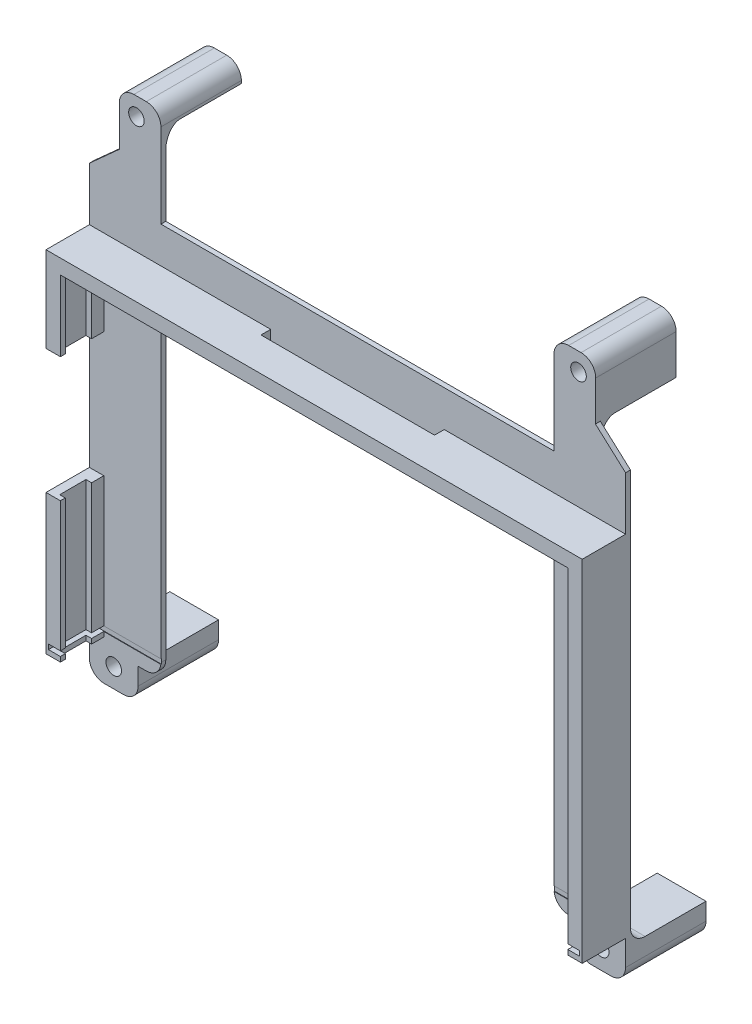
SolidWorks part; units mm, degrees
ref_plane "Front Plane" through (0, 0, 0) normal (1, 0, 0) x (0, 1, 0)
ref_plane "Top Plane" through (0, 0, 0) normal (0, 0, 1) x (0, 1, 0)
ref_plane "Right Plane" through (0, 0, 0) normal (0, 1, 0) x (-1, 0, 0)
sketch "Sketch1" plane through (0, 0, 0) normal (0, 0, 1) x (0, 1, 0)
  line L0 (-47.4715, -54.7542) -> (-54.0067, -54.7542)
  line L1 (-54.0067, -44.7542) -> (-54.0067, -54.7542)
  line L6 (-47.4715, -44.7542) -> (-54.0067, -44.7542)
  line L7 (-47.4715, -44.7542) -> (-47.4715, -54.7542)
  line L8 (42.478, -48.5761) -> (50.1367, -40.0774)
  line L9 (50.1367, -40.0774) -> (53.6912, -40.0774)
  line L10 (53.6912, -40.0774) -> (53.6912, -48.6408)
  line L11 (53.6912, -48.6408) -> (42.478, -48.5761)
  line L12 (53.6912, 49.1325) -> (42.478, 49.0678)
  line L13 (53.6912, 40.569) -> (53.6912, 49.1325)
  line L14 (50.1367, 40.569) -> (53.6912, 40.569)
  line L15 (42.478, 49.0678) -> (50.1367, 40.569)
  line L16 (-47.4715, 45.2458) -> (-47.4715, 55.2458)
  line L17 (-47.4715, 45.2458) -> (-54.0067, 45.2458)
  line L18 (-54.0067, 45.2458) -> (-54.0067, 55.2458)
  line L19 (-47.4715, 55.2458) -> (-54.0067, 55.2458)
  circle A0 centre (-50.0067, -49.7542) radius 1.6
  circle A1 centre (49.9933, -45.1018) radius 1.6
  circle A2 centre (49.9933, 45.5934) radius 1.6
  circle A3 centre (-50.0067, 50.2458) radius 1.6
extrude "Boss-Extrude1" add sketch "Sketch1" along normal blind 15.5
sketch "Sketch2" plane through (0, 0, 15.5) normal (0, 0, 1) x (1, 0, 0)
  line L0 (54.7542, -47.4715) -> (54.7542, -54.0067)
  line L1 (41.7542, -19.0067) -> (-42.2458, -19.0067) construction
  line L2 (-0.2458, -19.0067) -> (-0.2458, 62.4675) construction
  line L3 (-49.1325, 53.6912) -> (-49.0678, 42.478)
  line L4 (-40.569, 53.6912) -> (-49.1325, 53.6912)
  line L5 (44.7542, -54.0067) -> (54.7542, -54.0067)
  line L6 (44.7542, -47.4715) -> (44.7542, -54.0067)
  line L7 (40.0774, 53.6912) -> (40.0774, 33.4233)
  line L9 (-40.569, 53.6912) -> (-40.569, 33.4233)
  line L10 (-45.2458, -47.4715) -> (-40.569, -47.4715)
  line L11 (40.0774, 53.6912) -> (48.6408, 53.6912)
  line L12 (48.6408, 53.6912) -> (48.5761, 42.478)
  line L13 (-53.4458, -43.9132) -> (-53.4458, -44.8132)
  line L14 (-55.2458, -44.8132) -> (54.7542, -44.8132) construction
  line L15 (-45.2458, -47.4715) -> (-45.2458, -54.0067)
  line L16 (-45.2458, -54.0067) -> (-55.2458, -54.0067)
  line L17 (-55.2458, -47.4715) -> (-55.2458, -54.0067)
  line L18 (44.7542, -47.4715) -> (40.0774, -47.4715)
  line L19 (40.0774, -47.4715) -> (40.0774, 20.9868)
  line L20 (48.5761, 42.478) -> (54.7542, 36.9106)
  line L21 (54.7542, -47.4715) -> (54.7542, 36.9106)
  line L22 (40.0774, 20.9868) -> (-40.569, 20.9868)
  line L23 (40.0774, 33.4233) -> (-40.569, 33.4233)
  line L24 (-55.2458, -47.4715) -> (-55.2458, 36.9106)
  line L25 (-49.0678, 42.478) -> (-55.2458, 36.9106)
  line L26 (-40.569, -47.4715) -> (-40.569, 20.9868)
  line L27 (-52.317, -43.9132) -> (-52.317, -44.8132)
  line L28 (-49.1325, 53.6912) -> (-49.0678, 42.478)
  line L29 (-40.569, 53.6912) -> (-49.1325, 53.6912)
  line L31 (-53.4458, -43.9132) -> (52.9542, -43.9132) construction
  line L32 (52.9542, -43.9132) -> (52.9542, -44.8132)
  line L33 (-45.2458, -47.4715) -> (-45.2458, -54.0067)
  line L34 (-45.2458, -54.0067) -> (-55.2458, -54.0067)
  line L35 (-55.2458, -47.4715) -> (-55.2458, -54.0067)
  circle A0 centre (49.7542, -50.0067) radius 1.6
  circle A1 centre (45.1018, 49.9933) radius 1.6
  circle A2 centre (-45.5934, 49.9933) radius 1.6
  circle A3 centre (-50.2458, -50.0067) radius 1.6
  circle A4 centre (-45.5934, 49.9933) radius 1.6
  circle A5 centre (-50.2458, -50.0067) radius 1.6
  point P37 (-0.2458, 33.4233)
  point P38 (-0.2458, 20.9868)
  line M3 (48.5761, 42.478) -> (48.6408, 53.6912)
  line M4 (48.6408, 53.6912) -> (40.0774, 53.6912)
  line M5 (40.0774, 53.6912) -> (40.0774, 50.1367)
  line M6 (40.0774, 50.1367) -> (48.5761, 42.478)
  circle M7 centre (45.1018, 49.9933) radius 1.6
  dimension "D1" = 3.2
  dimension "D2" = 3.2
extrude "Boss-Extrude2" add sketch "Sketch2" along normal blind 1 contours L15 L26 L22 L19 L18 L6 L5 L0 L21 L20 L7 L23 L9 L4 L3 L25 L24 L17 L16 A2 A0 A3 M6 | M6 M3 M4 M5 M7 region at (53.2147, -50.7391, 15.5) region at (44.4212, 46.4122, 15.5)
sketch "Sketch3" plane through (0, 0, 16.5) normal (0, 0, 1) x (1, 0, 0)
  line L1 (-52.2958, 22.9868) -> (51.8042, 22.9868)
  line L2 (-52.2958, 22.9868) -> (-52.2958, 8.4399)
  line L3 (-52.2958, -42.8132) -> (-50.6497, -42.8132)
  line L4 (51.8042, 22.9868) -> (51.8042, -42.8132)
  line L5 (-52.2958, 22.9868) -> (51.8042, -42.8132) construction
  line L6 (-52.2958, -42.8132) -> (51.8042, 22.9868) construction
  line L20 (54.7542, 36.9106) -> (54.7542, -54.0067) construction
  line L21 (-55.2458, 25.9868) -> (54.7542, 25.9868)
  line L23 (40.0774, 20.9868) -> (-40.569, 20.9868) construction
  line L24 (-55.2458, 25.9868) -> (-55.2458, 8.4399)
  line L29 (-55.2458, -45.8132) -> (-52.2958, -45.8132)
  line L30 (54.7542, 25.9868) -> (54.7542, -45.8132)
  line L31 (-55.2458, 25.9868) -> (54.7542, -45.8132) construction
  line L32 (-55.2458, -45.8132) -> (54.7542, 25.9868) construction
  line L33 (-52.2958, -42.8132) -> (-52.2958, -45.8132)
  line L34 (51.8042, -42.8132) -> (51.8042, -45.8132)
  line L35 (51.8042, -45.8132) -> (54.7542, -45.8132)
  line L36 (50.1581, -42.8132) -> (51.8042, -42.8132)
  line L37 (-55.2458, 8.4399) -> (-52.2958, 8.4399)
  line L38 (-55.2458, -17.1408) -> (-52.2958, -17.1408)
  line L39 (-52.2958, -17.1408) -> (-52.2958, -42.8132)
  line L40 (-55.2458, -17.1408) -> (-55.2458, -45.8132)
  point P0 (-0.2458, -9.9132)
  point P5 (-0.2458, -9.9132)
  point P12 (-0.2458, -9.9132)
  point P20 (-0.2458, 20.9868)
  point P21 (-0.2458, -9.9132)
  line M14 (54.7542, -54.0067) -> (54.7542, 36.9106)
  line M24 (-55.2458, 36.9106) -> (-55.2458, -54.0067)
  dimension "D1" = 104.1
  dimension "D2" = 65.8
  dimension "D3" = 2
  dimension "D4" = 3
extrude "Boss-Extrude3" add sketch "Sketch3" along normal blind 2.5 contours L34 L35 L21 L29 L33 L2 L1 L4 M14 M24 | L33 L29 L40 L38 L39 region at (-53.6094, 15.7133, 16.5)
sketch "Sketch4" plane through (0, 0, 19) normal (0, 0, 1) x (1, 0, 0)
  line L0 (-0.2458, 22.9868) -> (-0.2458, -59.386) construction
  line L1 (-52.2958, 22.9868) -> (51.8042, 22.9868) construction
  line L2 (-55.2458, -45.8132) -> (54.7542, -45.8132) construction
  line L3 (-55.2458, 25.9868) -> (54.7542, 25.9868)
  line L4 (-55.2458, 25.9868) -> (-55.2458, 8.4399)
  line L5 (-55.2458, -45.8132) -> (-53.4458, -45.8132)
  line L6 (54.7542, 25.9868) -> (54.7542, -45.8132)
  line L7 (-55.2458, 25.9868) -> (54.7542, -45.8132) construction
  line L8 (-55.2458, -45.8132) -> (54.7542, 25.9868) construction
  line L9 (-53.4458, 24.0868) -> (52.9542, 24.0868)
  line L10 (-53.4458, 24.0868) -> (-53.4458, 8.4399)
  line L12 (52.9542, 24.0868) -> (52.9542, -43.9132)
  line L13 (-53.4458, 24.0868) -> (52.9542, -43.9132) construction
  line L14 (-53.4458, -43.9132) -> (52.9542, 24.0868) construction
  line L15 (-53.4458, -43.9132) -> (-53.4458, -45.8132)
  line L16 (52.9542, -43.9132) -> (52.9542, -45.8132)
  line L17 (52.9542, -45.8132) -> (54.7542, -45.8132)
  line L18 (-55.2458, 8.4399) -> (-53.4458, 8.4399)
  line L19 (-55.2458, 8.4399) -> (-52.2958, 8.4399) construction
  line L20 (-55.2458, -17.1408) -> (-53.4458, -17.1408)
  line L21 (-55.2458, -17.1408) -> (-52.2958, -17.1408) construction
  line L22 (-55.2458, -17.1408) -> (-55.2458, -45.8132)
  line L23 (-53.4458, -17.1408) -> (-53.4458, -43.9132)
  line L24 (-55.2458, -43.8132) -> (54.7542, -43.8132) construction
  point P4 (-0.2458, -9.9132)
  point P13 (-0.2458, -9.9132)
  dimension "D1" = 106.4
  dimension "D2" = 68
  dimension "D3" = 67.9
extrude "Boss-Extrude4" add sketch "Sketch4" along normal blind 5.4
sketch "Sketch5" plane through (0, 0, 24.4) normal (0, 0, 1) x (1, 0, 0)
  line L0 (-55.2458, 8.4399) -> (-52.2958, 8.4399)
  line L1 (-52.2958, 22.9868) -> (51.8042, 22.9868)
  line L2 (-52.2958, 22.9868) -> (-52.2958, 8.4399)
  line L4 (51.8042, 22.9868) -> (51.8042, -45.8132)
  line L5 (-55.2458, 25.9868) -> (54.7542, 25.9868)
  line L6 (-55.2458, 25.9868) -> (-55.2458, 8.4399)
  line L7 (-55.2458, -45.8132) -> (-52.2958, -45.8132)
  line L8 (54.7542, 25.9868) -> (54.7542, -45.8132)
  line L9 (-55.2458, -17.1408) -> (-52.2958, -17.1408)
  line L10 (51.8042, -45.8132) -> (54.7542, -45.8132)
  line L11 (-52.2958, -17.1408) -> (-52.2958, -45.8132)
  line L12 (-55.2458, -17.1408) -> (-55.2458, -45.8132)
extrude "Boss-Extrude5" add sketch "Sketch5" along normal blind 1
sketch "Sketch7" plane through (0, 0, 25.4) normal (0, 0, 1) x (1, 0, 0)
  line L0 (-54.7458, -43.8132) -> (54.2542, -43.8132)
  line L1 (54.2542, -43.8132) -> (54.2542, -44.8132)
  line L2 (54.2542, -44.8132) -> (-54.7458, -44.8132)
  line L3 (-54.7458, -44.8132) -> (-54.7458, -43.8132)
  line L4 (51.8042, -45.8132) -> (54.7542, -45.8132) construction
  line L5 (54.7542, -45.8132) -> (54.7542, 25.9868) construction
  line L6 (-55.2458, -17.1408) -> (-55.2458, -45.8132) construction
  dimension "D1" = 1
  dimension "D2" = 1
  dimension "D3" = 0.5
  dimension "D4" = 0.5
extrude "Cut-Extrude1" cut sketch "Sketch7" against normal blind 9
fillet "Fillet1" radius 3 10 edges at (48.6408, 53.6912, 8.25) (-49.1325, 53.6912, 8.25) (-40.569, -47.4715, 16) (-55.2458, -54.0067, 8.25) (-45.2458, -54.0067, 8.25) (40.0774, -47.4715, 16) (44.7542, -54.0067, 8.25) (54.7542, -54.0067, 8.25) (40.0774, 53.6912, 8.25) (-40.569, 53.6912, 8.25)
fillet "Fillet2" radius 3 4 edges at (-50.2458, -47.4715, 15.5) (-44.8184, 46.3073, 15.5) (44.3268, 46.3073, 15.5) (49.7542, -47.4715, 15.5)
sketch "Sketch8" plane through (0, 25.9868, 0) normal (0, 1, 0) x (-1, 0, 0)
  line L0 (-40.0774, 16.5) -> (40.569, 16.5) construction
  line L1 (-17.5542, 16.5) -> (18.0458, 16.5)
  line L2 (-17.5542, 16.5) -> (-17.5542, 18.5)
  line L3 (-17.5542, 18.5) -> (18.0458, 18.5)
  line L4 (18.0458, 16.5) -> (18.0458, 18.5)
  line L5 (0.2458, 25.4) -> (0.2458, 15.5) construction
  line L6 (-54.7542, 25.4) -> (55.2458, 25.4) construction
  line L7 (-40.0774, 15.5) -> (40.569, 15.5) construction
  dimension "D1" = 2
  dimension "D2" = 17.8
  dimension "D3" = 17.8
extrude "Cut-Extrude2" cut sketch "Sketch8" against normal blind 2
